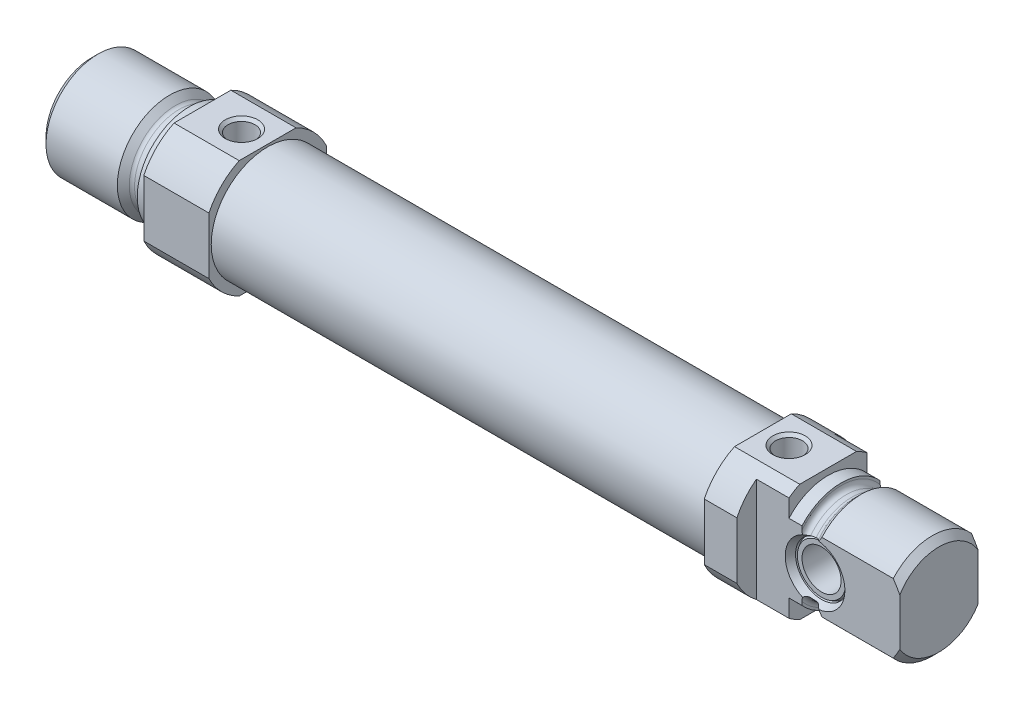
SolidWorks part; units mm, degrees
ref_plane "Front Plane" through (0, 0, 0) normal (0, 0, 1) x (1, 0, 0)
ref_plane "Top Plane" through (0, 0, 0) normal (0, 1, 0) x (1, 0, 0)
ref_plane "Right Plane" through (0, 0, 0) normal (1, 0, 0) x (0, 0, -1)
sketch "Sketch1" plane through (0, 0, 0) normal (0, 0, 1) x (1, 0, 0)
  line L0 (0, 0) -> (0, 7)
  line L1 (0, 7) -> (1, 8)
  line L2 (1, 8) -> (11.95, 8)
  line L3 (11.95, 8) -> (12.8657, 7.0843)
  line L4 (13.4314, 6.85) -> (14.2, 6.85)
  line L5 (15, 7.65) -> (15, 8)
  line L6 (15, 8) -> (17, 8)
  line L7 (17, 8) -> (17, 0)
  line L8 (17, 0) -> (0, 0)
  line L9 (17, 0) -> (0, 0) construction
  arc A0 (12.8657, 7.0843) -> (13.4314, 6.85) centre (13.4314, 7.65) ccw
  arc A1 (14.2, 6.85) -> (15, 7.65) centre (14.2, 7.65) ccw
revolve "Revolve1" add sketch "Sketch1" angle 360 about L9 reverse direction yes
cosmetic thread "Cosmetic Thread1" parameters "D1"=11.87, "D2"=14.16
ref_plane "Plane1" through (21.1, 0, 0) normal (1, 0, 0) x (0, 0, -1)
ref_plane "Plane2" through (9, 0, 0) normal (1, 0, 0) x (0, 0, -1)
ref_plane "Plane3" through (0, -11, 0) normal (0, 1, 0) x (1, 0, 0)
ref_plane "Plane4" through (0, 11, 0) normal (0, 1, 0) x (1, 0, 0)
ref_plane "Plane5" through (0, 0, 0) normal (0, 1, 0) x (1, 0, 0)
ref_plane "Plane6" through (0, 0, 0) normal (0, 1, 0) x (1, 0, 0)
ref_plane "Plane7" through (17, 0, 0) normal (1, 0, 0) x (0, 0, -1)
ref_plane "Plane8" through (17, 0, 0) normal (1, 0, 0) x (0, 0, -1)
ref_plane "Plane9" through (27, 0, 0) normal (1, 0, 0) x (0, 0, -1)
ref_plane "Plane10" through (17, 0, 0) normal (1, 0, 0) x (0, 0, -1)
ref_plane "Plane11" through (17, 0, 0) normal (1, 0, 0) x (0, 0, -1)
sketch "Sketch2" plane through (17, 0, 0) normal (1, 0, 0) x (0, 0, -1)
  line L0 (-4.3589, -9) -> (4.3589, -9)
  line L1 (9, -4.3589) -> (9, 4.3589)
  line L2 (4.3589, 9) -> (-4.3589, 9)
  line L3 (-9, 4.3589) -> (-9, -4.3589)
  arc A0 (-9, -4.3589) -> (-4.3589, -9) centre (0, 0) ccw
  arc A1 (4.3589, -9) -> (9, -4.3589) centre (0, 0) ccw
  arc A2 (9, 4.3589) -> (4.3589, 9) centre (0, 0) ccw
  arc A3 (-4.3589, 9) -> (-9, 4.3589) centre (0, 0) ccw
extrude "Boss-Extrude1" add sketch "Sketch2" along normal blind 10
ref_plane "Plane12" through (23, 0, 0) normal (1, 0, 0) x (0, 0, -1)
ref_plane "Plane13" through (0, 0, 0) normal (0, 0, 1) x (1, 0, 0)
ref_plane "Plane14" through (0, 0, -5.8) normal (0, 0, 1) x (1, 0, 0)
ref_plane "Plane15" through (0, 0, 0) normal (0, 1, 0) x (1, 0, 0)
ref_plane "Plane16" through (0, 4.5, 0) normal (0, 1, 0) x (1, 0, 0)
ref_plane "Plane17" through (0, 0, -6.6) normal (0, 0, 1) x (1, 0, 0)
ref_plane "Plane18" through (0, 0, 0) normal (0, 1, 0) x (1, 0, 0)
ref_plane "Plane19" through (0, 4.5, 0) normal (0, 1, 0) x (1, 0, 0)
ref_plane "Plane20" through (0, 5.493, -0.9686) normal (0, 0.9848, -0.1736) x (1, 0, 0)
ref_plane "Plane21" through (0, 4.0158, -0.7081) normal (0, 0.9848, -0.1736) x (1, 0, 0)
sketch "Sketch3" plane through (0, 0, 0) normal (0, 0, 1) x (1, 0, 0)
  line L0 (27, 0) -> (27, 8.65)
  line L1 (27, 8.65) -> (103, 8.65)
  line L2 (103, 8.65) -> (103, 0)
  line L3 (103, 0) -> (27, 0)
  line L4 (103, 0) -> (27, 0) construction
revolve "Revolve2" add sketch "Sketch3" angle 360 about L4 reverse direction yes
ref_plane "Plane22" through (103, 0, 0) normal (1, 0, 0) x (0, 0, -1)
sketch "Sketch4" plane through (103, 0, 0) normal (1, 0, 0) x (0, 0, -1)
  line L0 (-9, -9) -> (9, -9)
  line L1 (9, -9) -> (9, 9)
  line L2 (9, 9) -> (-9, 9)
  line L3 (-9, 9) -> (-9, -9)
extrude "Boss-Extrude2" add sketch "Sketch4" along normal blind 10
sketch "Sketch5" plane through (0, 0, 0) normal (0, 0, 1) x (1, 0, 0)
  line L0 (103, 20) -> (103, 10)
  line L1 (103, 10) -> (113, 10)
  line L2 (113, 10) -> (113, 20)
  line L3 (113, 20) -> (103, 20)
  line L4 (113, 0) -> (103, 0) construction
revolve "Cut-Revolve1" cut sketch "Sketch5" angle 360 about L4 reverse direction yes
ref_plane "Plane23" through (105.3, 0, 0) normal (1, 0, 0) x (0, 0, -1)
ref_plane "Plane24" through (107, 0, 0) normal (1, 0, 0) x (0, 0, -1)
ref_plane "Plane25" through (0, 0, 6.6) normal (0, 0, 1) x (1, 0, 0)
ref_plane "Plane26" through (0, 0, 0) normal (0, 1, 0) x (1, 0, 0)
ref_plane "Plane27" through (0, 4.5, 0) normal (0, 1, 0) x (1, 0, 0)
ref_plane "Plane28" through (0, 5.493, 0.9686) normal (0, 0.9848, 0.1736) x (1, 0, 0)
ref_plane "Plane29" through (0, 4.0158, 0.7081) normal (0, 0.9848, 0.1736) x (1, 0, 0)
ref_plane "Plane30" through (151, 0, 0) normal (1, 0, 0) x (0, 0, -1)
sketch "Sketch6" plane through (0, 0, 0) normal (0, 0, 1) x (1, 0, 0)
  line L0 (113, 0) -> (113, 8)
  line L1 (113, 8) -> (115, 8)
  line L2 (115, 8) -> (115, 7.65)
  line L3 (115.8, 6.85) -> (116.5686, 6.85)
  line L4 (117.1343, 7.0843) -> (118.05, 8)
  line L5 (118.05, 8) -> (129, 8)
  line L6 (129, 8) -> (130, 7)
  line L7 (130, 7) -> (130, 0)
  line L8 (130, 0) -> (113, 0)
  line L9 (130, 0) -> (113, 0) construction
  arc A0 (115, 7.65) -> (115.8, 6.85) centre (115.8, 7.65) ccw
  arc A1 (116.5686, 6.85) -> (117.1343, 7.0843) centre (116.5686, 7.65) ccw
revolve "Revolve3" add sketch "Sketch6" angle 360 about L9 reverse direction yes
cosmetic thread "Cosmetic Thread2" parameters "D1"=11.87, "D2"=14.16
ref_plane "Plane31" through (141, 0, 0) normal (1, 0, 0) x (0, 0, -1)
ref_plane "Plane32" through (151, 0, 0) normal (1, 0, 0) x (0, 0, -1)
ref_plane "Plane33" through (151, 0, 0) normal (1, 0, 0) x (0, 0, -1)
sketch "Sketch7" plane through (0, 0, 0) normal (0, 1, 0) x (1, 0, 0)
  line L0 (108, 18) -> (108, 6)
  line L1 (108, 6) -> (130, 6)
  line L2 (130, 6) -> (130, -6)
  line L3 (130, -6) -> (108, -6)
  line L4 (108, -6) -> (108, -18)
  line L5 (108, -18) -> (142, -18)
  line L6 (142, -18) -> (142, 18)
  line L7 (142, 18) -> (108, 18)
extrude "Cut-Extrude1" cut sketch "Sketch7" along normal blind 10 and the other way blind 10
ref_plane "Plane34" through (117, 0, 0) normal (1, 0, 0) x (0, 0, -1)
sketch "Sketch8" plane through (117, 0, 0) normal (1, 0, 0) x (0, 0, -1)
  line L0 (-6.2, 0) -> (-6.2, 4.6928)
  line L1 (-6.2, 4.6928) -> (-5, 4)
  line L2 (-5, 4) -> (-4.5, 4)
  line L3 (-4.5, 4) -> (-5, 3.7113)
  line L4 (-5, 3.7113) -> (-5, 3)
  line L5 (-5, 3) -> (5, 3)
  line L6 (5, 3) -> (5, 3.7113)
  line L7 (5, 3.7113) -> (4.5, 4)
  line L8 (4.5, 4) -> (5, 4)
  line L9 (5, 4) -> (6.2, 4.6928)
  line L10 (6.2, 4.6928) -> (6.2, 0)
  line L11 (6.2, 0) -> (-6.2, 0)
  line L12 (5, 0) -> (-6.2, 0) construction
revolve "Cut-Revolve2" cut sketch "Sketch8" angle 360 about L12 reverse direction yes
hole_wizard "Hole1" positions "Sketch10" profile "Sketch9" legacy
sketch "Sketch10" plane through (0, 9, 0) normal (0, 1, 0) x (1, 0, 0)
  point P0 (23, 0)
sketch "Sketch9" plane through (23, 9, 0) normal (1, 0, 0) x (0, 0, 1)
  line L0 (0, 0) -> (0, 9)
  line L1 (0, 9) -> (2.067, 9)
  line L2 (2.067, 9) -> (2.067, 0.433)
  line L3 (2.067, 0.433) -> (2.5, 0)
  line L4 (2.5, 0) -> (0, 0)
  line L5 (0, -6.4453) -> (0, 115.525) construction
  line L6 (-2.067, 0.433) -> (-2.5, 0) construction
  dimension "Diameter" = 4.134
  dimension "Depth" = 9
  dimension "C-Sink Angle" = 90
  dimension "C-Sink Diameter" = 5
cosmetic thread "Cosmetic Thread3" parameters "D1"=7, "D2"=5
hole_wizard "Hole2" positions "Sketch12" profile "Sketch11" legacy
sketch "Sketch12" plane through (0, 9, 0) normal (0, 1, 0) x (1, 0, 0)
  point P0 (107, 0)
sketch "Sketch11" plane through (107, 9, 0) normal (1, 0, 0) x (0, 0, 1)
  line L0 (0, 0) -> (0, 12.1934)
  line L1 (0, 12.1934) -> (2.067, 11)
  line L2 (2.067, 11) -> (2.067, 0.433)
  line L3 (2.067, 0.433) -> (2.5, 0)
  line L4 (2.5, 0) -> (0, 0)
  line L5 (0, -14.3089) -> (0, 102.4216) construction
  line L6 (0, 12.1934) -> (-2.067, 11) construction
  line L7 (-2.067, 0.433) -> (-2.5, 0) construction
  dimension "Diameter" = 4.134
  dimension "Depth" = 11
  dimension "C-Sink Diameter" = 5
  dimension "C-Sink Angle" = 90
  dimension "Drill Angle" = 120
cosmetic thread "Cosmetic Thread4" parameters "D1"=6, "D2"=5
sketch "Sketch13" plane through (0, 0, 0) normal (0, 0, 1) x (1, 0, 0)
  line L0 (-5, 0) -> (-5, 3)
  line L1 (-5, 3) -> (41.2, 3)
  line L2 (41.2, 3) -> (41.2, 8)
  line L3 (41.2, 8) -> (85.2, 8)
  line L4 (85.2, 8) -> (85.2, 0)
  line L5 (85.2, 0) -> (-5, 0)
  line L6 (85.2, 0) -> (-5, 0) construction
revolve "Cut-Revolve3" cut sketch "Sketch13" angle 360 about L6 reverse direction yes
ref_plane "Plane35" through (-5, 0, 0) normal (1, 0, 0) x (0, 0, -1)
ref_plane "Plane36" through (0, 10, 0) normal (0, 1, 0) x (1, 0, 0)
ref_plane "Plane37" through (7, 0, 0) normal (1, 0, 0) x (0, 0, -1)
ref_plane "Plane38" through (0, 0, 0) normal (1, 0, 0) x (0, 0, -1)
ref_plane "Plane39" through (17, 0, 0) normal (1, 0, 0) x (0, 0, -1)
ref_plane "Plane40" through (113, 0, 0) normal (1, 0, 0) x (0, 0, -1)
ref_plane "Plane41" through (17, 0, 0) normal (1, 0, 0) x (0, 0, -1)
ref_plane "Plane42" through (0, 9, 0) normal (0, 1, 0) x (1, 0, 0)
ref_plane "Plane43" through (36.5, 0, 0) normal (1, 0, 0) x (0, 0, -1)
ref_plane "Plane44" through (93.5, 0, 0) normal (1, 0, 0) x (0, 0, -1)
ref_plane "Plane45" through (0, 0, 0) normal (0, 0, 1) x (1, 0, 0)
ref_plane "Plane46" through (17, 0, 0) normal (1, 0, 0) x (0, 0, -1)
ref_plane "Plane47" through (0, 9, 0) normal (0, 1, 0) x (1, 0, 0)
ref_plane "FDT_FRONT XY" through (17, 0, 0) normal (1, 0, 0) x (0, 0, -1)
ref_plane "FDT_FRONT XZ" through (0, 0, 0) normal (0, -1, 0) x (-1, 0, 0)
ref_plane "FDT_FRONT YZ" through (0, 0, 0) normal (0, 0, -1) x (-1, 0, 0)
ref_axis "FDT_FRONT X" through (17, 0, 80.9) along (0, 0, -1)
ref_axis "FDT_FRONT Y" through (17, -50, 0) along (0, 1, 0)
ref_axis "FDT_FRONT Z" through (80.9, 0, 0) along (-1, 0, 0)
sketch3d "FDT_FRONT"
  point P0 (17, 0, 0)
ref_plane "FDT_QSFRONT XY" through (0, 9, 0) normal (0, 1, 0) x (1, 0, 0)
ref_plane "FDT_QSFRONT XZ" through (23, 0, 0) normal (-1, 0, 0) x (0, 0, 1)
ref_plane "FDT_QSFRONT YZ" through (0, 0, 0) normal (0, 0, 1) x (1, 0, 0)
ref_axis "FDT_QSFRONT X" through (23, 9, -50) along (0, 0, 1)
ref_axis "FDT_QSFRONT Y" through (-80.9, 9, 0) along (1, 0, 0)
ref_axis "FDT_QSFRONT Z" through (23, 50, 0) along (0, -1, 0)
sketch3d "FDT_QSFRONT"
  point P0 (23, 9, 0)
ref_plane "FDT_QSREAR XY" through (0, 9, 0) normal (0, 1, 0) x (1, 0, 0)
ref_plane "FDT_QSREAR XZ" through (107, 0, 0) normal (-1, 0, 0) x (0, 0, 1)
ref_plane "FDT_QSREAR YZ" through (0, 0, 0) normal (0, 0, 1) x (1, 0, 0)
ref_axis "FDT_QSREAR X" through (107, 9, -50) along (0, 0, 1)
ref_axis "FDT_QSREAR Y" through (-80.9, 9, 0) along (1, 0, 0)
ref_axis "FDT_QSREAR Z" through (107, 50, 0) along (0, -1, 0)
sketch3d "FDT_QSREAR"
  point P0 (107, 9, 0)
ref_plane "FDT_REAR XY" through (113, 0, 0) normal (-1, 0, 0) x (0, 0, 1)
ref_plane "FDT_REAR XZ" through (0, 0, 0) normal (0, 1, 0) x (1, 0, 0)
ref_plane "FDT_REAR YZ" through (0, 0, 0) normal (0, 0, -1) x (-1, 0, 0)
ref_axis "FDT_REAR X" through (113, 0, 80.9) along (0, 0, -1)
ref_axis "FDT_REAR Y" through (113, 50, 0) along (0, -1, 0)
ref_axis "FDT_REAR Z" through (-80.9, 0, 0) along (1, 0, 0)
sketch3d "FDT_REAR"
  point P0 (113, 0, 0)
ref_plane "FDT_SMBR1 XY" through (36.5, 0, 0) normal (-1, 0, 0) x (0, 0, 1)
ref_plane "FDT_SMBR1 XZ" through (0, 0, 0) normal (0, -1, 0) x (-1, 0, 0)
ref_plane "FDT_SMBR1 YZ" through (0, 0, 0) normal (0, 0, 1) x (1, 0, 0)
ref_axis "FDT_SMBR1 X" through (36.5, 0, -80.9) along (0, 0, 1)
ref_axis "FDT_SMBR1 Y" through (36.5, -50, 0) along (0, 1, 0)
ref_axis "FDT_SMBR1 Z" through (-80.9, 0, 0) along (1, 0, 0)
sketch3d "FDT_SMBR1"
  point P0 (36.5, 0, 0)
ref_plane "FDT_SMBR2 XY" through (93.5, 0, 0) normal (-1, 0, 0) x (0, 0, 1)
ref_plane "FDT_SMBR2 XZ" through (0, 0, 0) normal (0, -1, 0) x (-1, 0, 0)
ref_plane "FDT_SMBR2 YZ" through (0, 0, 0) normal (0, 0, 1) x (1, 0, 0)
ref_axis "FDT_SMBR2 X" through (93.5, 0, -80.9) along (0, 0, 1)
ref_axis "FDT_SMBR2 Y" through (93.5, -50, 0) along (0, 1, 0)
ref_axis "FDT_SMBR2 Z" through (-80.9, 0, 0) along (1, 0, 0)
sketch3d "FDT_SMBR2"
  point P0 (93.5, 0, 0)
ref_plane "FDT_SWIVELAXIS XY" through (0, 0, 0) normal (0, 0, 1) x (1, 0, 0)
ref_plane "FDT_SWIVELAXIS XZ" through (0, 0, 0) normal (0, -1, 0) x (-1, 0, 0)
ref_plane "FDT_SWIVELAXIS YZ" through (117, 0, 0) normal (1, 0, 0) x (0, 0, -1)
ref_axis "FDT_SWIVELAXIS X" through (-80.9, 0, 0) along (1, 0, 0)
ref_axis "FDT_SWIVELAXIS Y" through (117, -50, 0) along (0, 1, 0)
ref_axis "FDT_SWIVELAXIS Z" through (117, 0, 80.9) along (0, 0, -1)
sketch3d "FDT_SWIVELAXIS"
  point P0 (117, 0, 0)
ref_plane "NUT XY" through (7, 0, 0) normal (1, 0, 0) x (0, 0, -1)
ref_plane "NUT XZ" through (0, 0, 0) normal (0, -1, 0) x (-1, 0, 0)
ref_plane "NUT YZ" through (0, 0, 0) normal (0, 0, -1) x (-1, 0, 0)
ref_axis "NUT X" through (7, 0, 80.9) along (0, 0, -1)
ref_axis "NUT Y" through (7, -50, 0) along (0, 1, 0)
ref_axis "NUT Z" through (80.9, 0, 0) along (-1, 0, 0)
sketch3d "NUT"
  point P0 (7, 0, 0)
ref_plane "ZR XY" through (0, 0, 0) normal (-1, 0, 0) x (0, 0, 1)
ref_plane "ZR XZ" through (0, 0, 0) normal (0, 1, 0) x (1, 0, 0)
ref_plane "ZR YZ" through (0, 0, 0) normal (0, 0, -1) x (-1, 0, 0)
ref_axis "ZR X" through (0, 0, 80.9) along (0, 0, -1)
ref_axis "ZR Y" through (0, 50, 0) along (0, -1, 0)
ref_axis "ZR Z" through (-80.9, 0, 0) along (1, 0, 0)
sketch3d "ZR"
  point P0 (0, 0, 0)
ref_plane "ZYL XY" through (17, 0, 0) normal (1, 0, 0) x (0, 0, -1)
ref_plane "ZYL XZ" through (0, 0, 0) normal (0, -1, 0) x (-1, 0, 0)
ref_plane "ZYL YZ" through (0, 0, 0) normal (0, 0, -1) x (-1, 0, 0)
ref_axis "ZYL X" through (17, 0, 80.9) along (0, 0, -1)
ref_axis "ZYL Y" through (17, -50, 0) along (0, 1, 0)
ref_axis "ZYL Z" through (80.9, 0, 0) along (-1, 0, 0)
sketch3d "ZYL"
  point P0 (17, 0, 0)
